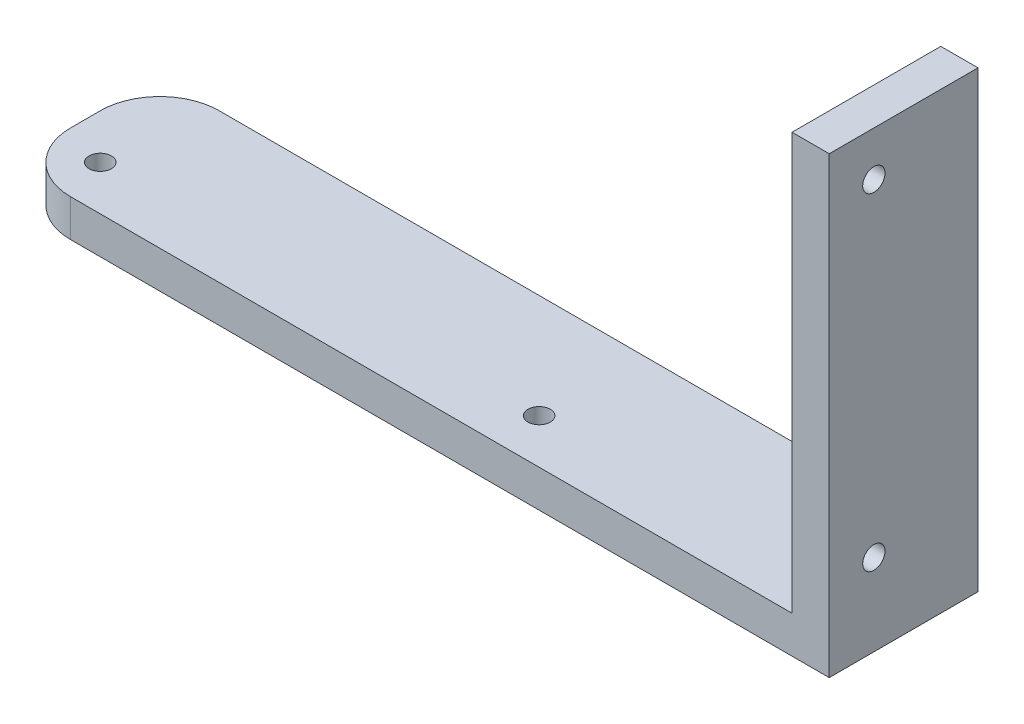
SolidWorks part; units mm, degrees
ref_plane "Front Plane" through (0, 0, 0) normal (0, 0, 1) x (1, 0, 0)
ref_plane "Top Plane" through (0, 0, 0) normal (0, 1, 0) x (1, 0, 0)
ref_plane "Right Plane" through (0, 0, 0) normal (1, 0, 0) x (0, 0, -1)
sketch "Sketch1" plane through (0, 0, 0) normal (0, 1, 0) x (1, 0, 0)
  line L1 (0, 0) -> (110, 0)
  line L2 (0, 0) -> (0, 20)
  line L3 (0, 20) -> (110, 20)
  line L4 (110, 0) -> (110, 20)
  dimension "D1" = 110
  dimension "D2" = 20
extrude "Boss-Extrude1" add sketch "Sketch1" along normal blind 5
sketch "Sketch2" plane through (0, 5, 0) normal (0, 1, 0) x (1, 0, 0)
  line L0 (110, 20) -> (0, 20) construction
  line L1 (110, 0) -> (105, 0)
  line L2 (110, 0) -> (110, 20)
  line L3 (110, 20) -> (105, 20)
  line L4 (105, 0) -> (105, 20)
  dimension "D1" = 5
extrude "Boss-Extrude2" add sketch "Sketch2" along normal blind 56
sketch "Sketch3" plane through (0, 5, 0) normal (0, 1, 0) x (1, 0, 0)
  line L0 (0, 20) -> (0, 0) construction
  line L1 (0, 0) -> (105, 0) construction
  circle A0 centre (6, 6) radius 1.5
  circle A1 centre (65, 6) radius 1.5
  dimension "D1" = 3
  dimension "D2" = 6
  dimension "D3" = 6
  dimension "D4" = 59
extrude "Cut-Extrude1" cut sketch "Sketch3" against normal through all
fillet "Fillet1" radius 8 2 edges at (0, 2.5, 0) (0, 2.5, -20)
sketch "Sketch4" plane through (105, 0, 0) normal (-1, 0, 0) x (0, 0, 1)
  line L1 (-20, 5) -> (0, 5) construction
  line L3 (0, 61) -> (0, 5) construction
  circle A0 centre (-6, 11) radius 1.5
  circle A2 centre (-6, 55) radius 1.5
  dimension "D1" = 6
  dimension "D2" = 3
  dimension "D3" = 6
  dimension "D4" = 44
extrude "Cut-Extrude2" cut sketch "Sketch4" against normal through all
